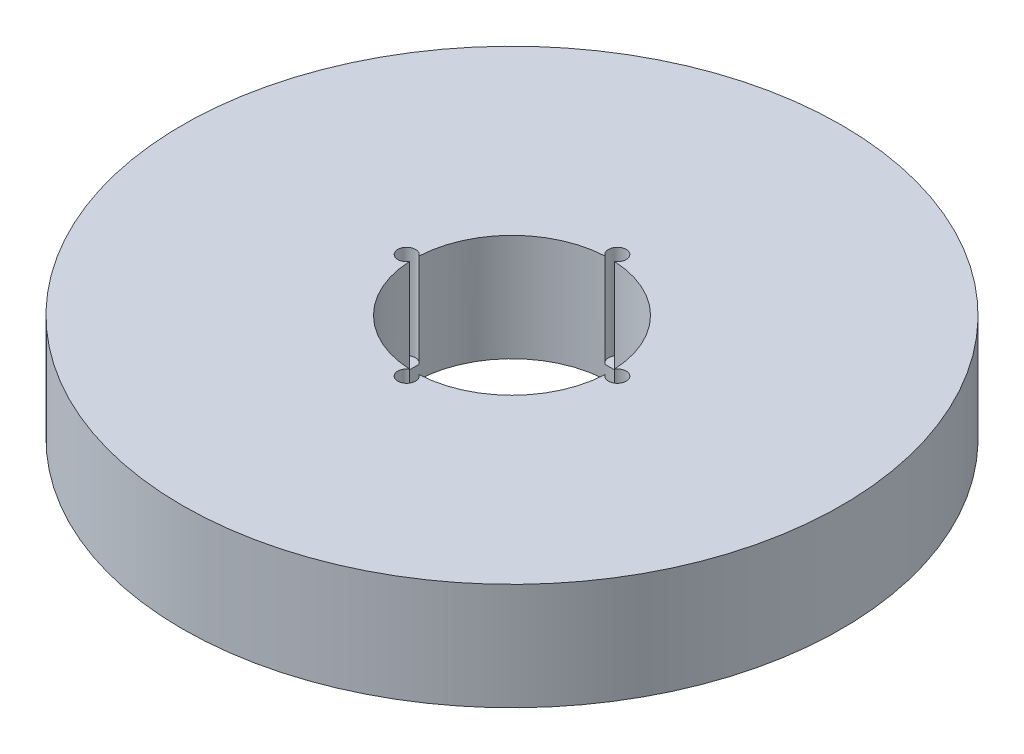
SolidWorks part; units mm, degrees
ref_plane "Front Plane" through (0, 0, 0) normal (0, 0, 1) x (1, 0, 0)
ref_plane "Top Plane" through (0, 0, 0) normal (0, 1, 0) x (1, 0, 0)
ref_plane "Right Plane" through (0, 0, 0) normal (1, 0, 0) x (0, 0, -1)
sketch "Sketch1" plane through (0, 0, 0) normal (0, 1, 0) x (1, 0, 0)
  circle A0 centre (0, 0) radius 92.5
  dimension "FLANGE_OD" = 185
extrude "Boss-Extrude1" add sketch "Sketch1" along normal blind 30
sketch "Sketch2" plane through (0, 0, 0) normal (0, 1, 0) x (1, 0, 0)
  circle A0 centre (0, 0) radius 27.5
  dimension "BORE_D" = 55
extrude "Cut-Extrude1" cut sketch "Sketch2" along normal through all
sketch "Sketch3" plane through (0, 30, 0) normal (0, 1, 0) x (1, 0, 0)
  circle A0 centre (0, 0) radius 29.572 construction
  circle A1 centre (-29.572, 0) radius 2.4778
  dimension "BOLT_D" = 4.9555
  dimension "BOLT_PCD" = 59.1439
extrude "Cut-Extrude2" cut sketch "Sketch3" against normal blind 26.3607
pattern_circular "CirPattern1" count 4 over 360 about axis through (0, 0, 0) along (0, 1, 0) of "Cut-Extrude2"
